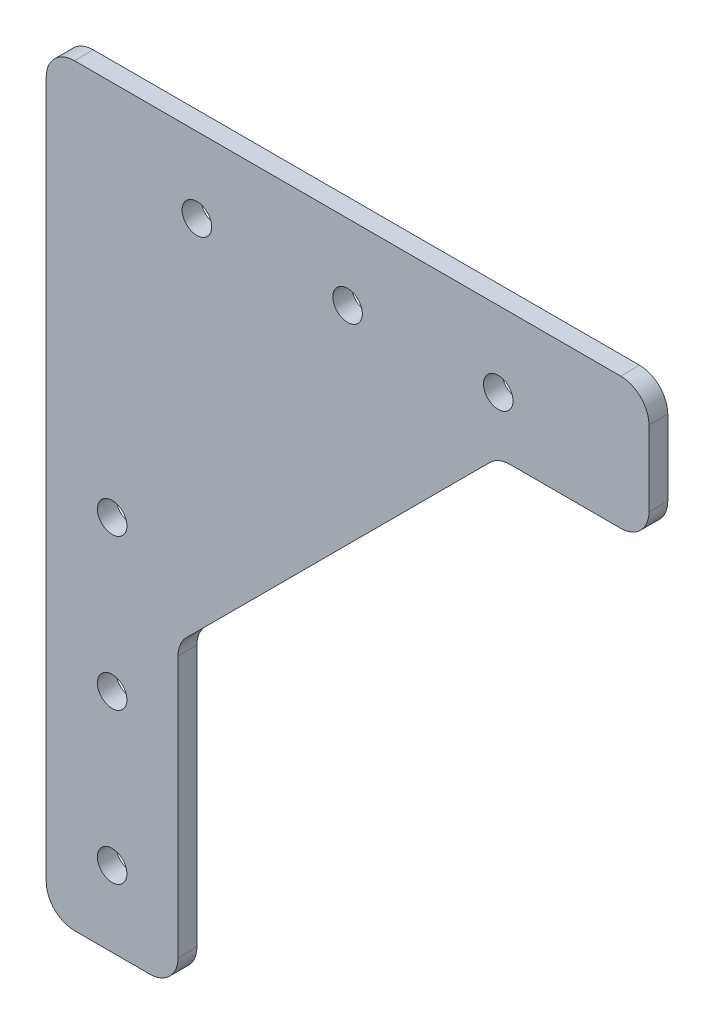
SolidWorks part; units mm, degrees
material "6061-T6 (SS)"
ref_plane "Front Plane" through (0, 0, 0) normal (0, 0, 1) x (1, 0, 0)
ref_plane "Top Plane" through (0, 0, 0) normal (0, 1, 0) x (1, 0, 0)
ref_plane "Right Plane" through (0, 0, 0) normal (1, 0, 0) x (0, 0, -1)
sketch "Sketch1" plane through (0, 0, 0) normal (0, 0, 1) x (1, 0, 0)
  line L8 (0, 0) -> (0, 127)
  line L14 (0, 127) -> (101.6, 127)
  line L15 (101.6, 127) -> (101.6, 104.775)
  line L17 (22.225, 0) -> (0, 0)
  line L18 (11.1125, 0) -> (11.1125, 127) construction
  line L19 (22.225, 0) -> (22.225, 50.8)
  line L20 (22.225, 50.8) -> (76.2, 104.775)
  line L21 (76.2, 104.775) -> (101.6, 104.775)
  circle A7 centre (11.1125, 63.5) radius 2.4892
  circle A8 centre (11.1125, 38.1) radius 2.4892
  circle A9 centre (11.1125, 12.7) radius 2.4892
  circle A11 centre (76.2, 114.3) radius 2.4892
  circle A12 centre (50.8, 114.3) radius 2.4892
  circle A13 centre (25.4, 114.3) radius 2.4892
  point P21 (25.4, 50.981)
  point P22 (25.4, 56.7402)
  point P23 (22.225, 100.5232)
  dimension "D5" = 4.9784
  dimension "D7" = 12.7
  dimension "D1" = 22.225
  dimension "D2" = 127
  dimension "D3" = 101.6
  dimension "D4" = 3
  dimension "D6" = 25.4
  dimension "D8" = 3
  dimension "D9" = 12.7
  dimension "D10" = 25.4
  dimension "D11" = 25.4
  dimension "D12" = 45
  dimension "D13" = 25.4
extrude "Boss-Extrude1" add sketch "Sketch1" along normal mid plane 3.175 contours L18 A7 | A7 L18 | L18 A9 | A9 L18 | A11 | L8 L14 L15 L21 L20 L19 L17 | A8 | A12 | A13 region at (10.0561, 12.7, 0) region at (12.1689, 12.7, 0) region at (12.1689, 63.5, 0) region at (10.0561, 63.5, 0) region at (76.2, 114.3, 0)
fillet "Fillet1" radius 4.7625 7 edges at (0, 127, 0) (0, 0, 0) (101.6, 104.775, 0) (76.2, 104.775, 0) (22.225, 50.8, 0) (22.225, 0, 0) (101.6, 127, 0)
